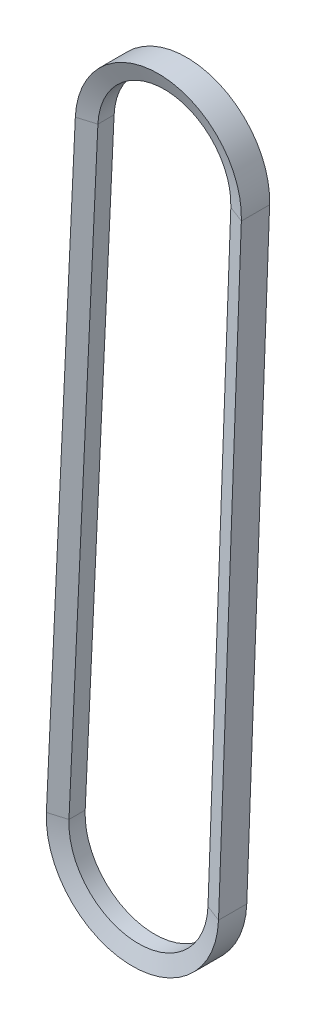
SolidWorks part; units mm, degrees
ref_plane "Front Plane" through (0, 0, 0) normal (0, 0, 1) x (1, 0, 0)
ref_plane "Top Plane" through (0, 0, 0) normal (0, 1, 0) x (1, 0, 0)
ref_plane "Right Plane" through (0, 0, 0) normal (1, 0, 0) x (0, 0, -1)
sketch "Sketch2" plane through (0, 0, 0) normal (0, 0, 1) x (1, 0, 0)
  line L0 (0, 0) -> (1, 0) construction
  line L1 (0, 0) -> (0, 1) construction
  line L2 (27.9808, -1.0361) -> (20.2844, -208.8911)
  line L3 (-37.715, -206.4571) -> (-27.9692, 1.3119)
  arc A0 (-27.9692, 1.3119) -> (27.9808, -1.0361) centre (0, 0) cw
  arc A1 (20.2844, -208.8911) -> (-37.715, -206.4571) centre (-8.7213, -207.8171) cw
ref_plane "Plane4" through (27.9808, -1.0361, 0) normal (-0.037, -0.9993, 0) x (-0.9993, 0.037, 0)
sketch "Sketch3" plane through (27.9808, -1.0361, 0) normal (-0.037, -0.9993, 0) x (-0.9993, 0.037, 0)
  line L0 (0, 4.7625) -> (0, -4.7625)
  line L1 (0, 4.7625) -> (5.588, 2.7286)
  line L2 (5.588, 2.7286) -> (5.588, -2.7286)
  line L3 (5.588, -2.7286) -> (0, -4.7625)
  line L4 (0, 0) -> (5.588, 0) construction
  point P2 (0, 0)
  dimension "D1" = 9.525
  dimension "D2" = 5.588
  dimension "D3" = 40
sweep "Sweep1" add profiles "Sketch3" path "Sketch2"
